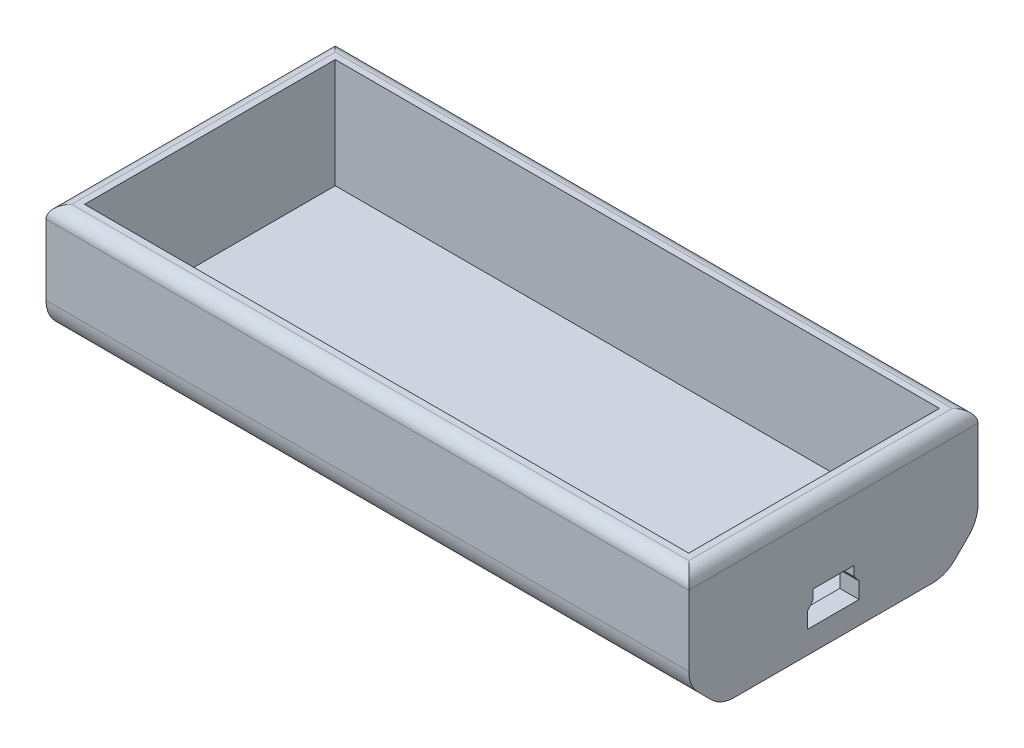
SolidWorks part; units mm, degrees
ref_plane "Front Plane" through (0, 0, 0) normal (0, 0, 1) x (1, 0, 0)
ref_plane "Top Plane" through (0, 0, 0) normal (0, 1, 0) x (1, 0, 0)
ref_plane "Right Plane" through (0, 0, 0) normal (1, 0, 0) x (0, 0, -1)
sketch "Sketch1" plane through (0, 0, 0) normal (0, 1, 0) x (1, 0, 0)
  line L1 (-50, 22.5) -> (50, 22.5)
  line L2 (-50, 22.5) -> (-50, -22.5)
  line L3 (-50, -22.5) -> (50, -22.5)
  line L4 (50, 22.5) -> (50, -22.5)
  line L5 (0, -22.5) -> (0, 22.5) construction
  line L6 (-50, 0) -> (50, 0) construction
  point P0 (0, 0)
  dimension "D1" = 100
  dimension "D2" = 45
extrude "Boss-Extrude1" add sketch "Sketch1" along normal blind 20
shell "Shell1" thickness 3 removed face at (0, 20, 0)
chamfer "Chamfer1" distance 5 angle 45 2 edges at (0, 0, -22.5) (0, 0, 22.5)
fillet "Fillet1" radius 5 4 edges at (0, 5, -22.5) (0, 0, -17.5) (0, 0, 17.5) (0, 5, 22.5)
fillet "Fillet2" radius 1 1 edges at (-50, 0, 0) tangent propagation no
shell "Shell2" thickness 3 rebuild error yes
fillet "Fillet5" radius 2 4 edges at (50, 20, 0) (0, 20, -22.5) (-50, 20, 0) (0, 20, 22.5)
sketch "Sketch4" plane through (50, 0, 0) normal (1, 0, 0) x (0, 0, -1)
  line L0 (3.2, 7) -> (3.2, 8.5)
  line L1 (-3.2, 8.5) -> (-3.2, 7)
  line L3 (0, 20) -> (0, 18.2355)
  line L4 (-20.5, 20) -> (20.5, 20) construction
  line L5 (-15.4289, 0) -> (15.4289, 0) construction
  line L6 (-4, 6) -> (-3.2, 7)
  line L7 (-4, 3.5) -> (4, 3.5)
  line L11 (-3.2, 8.5) -> (3.2, 8.5)
  line L14 (4, 6) -> (3.2, 7)
  line L15 (4, 6) -> (4, 3.5)
  line L16 (-4, 6) -> (-4, 3.5)
  point P21 (-3.2, 8.5)
  point P25 (3.2, 8.5)
  dimension "D1" = 1.5
  dimension "D2" = 0.8
  dimension "D3" = 1
  dimension "D4" = 8.5
  dimension "D5" = 1.5
  dimension "D6" = 8
  dimension "D7" = 2.5
  dimension "D8" = 1
  dimension "D9" = 1.5
  dimension "D10" = 1.2806
extrude "Cut-Extrude4" cut sketch "Sketch4" against normal blind 29 contours L6 L16 L7 L15 L14 L0 L11 L1 region at (50, 5.8714, 0)
